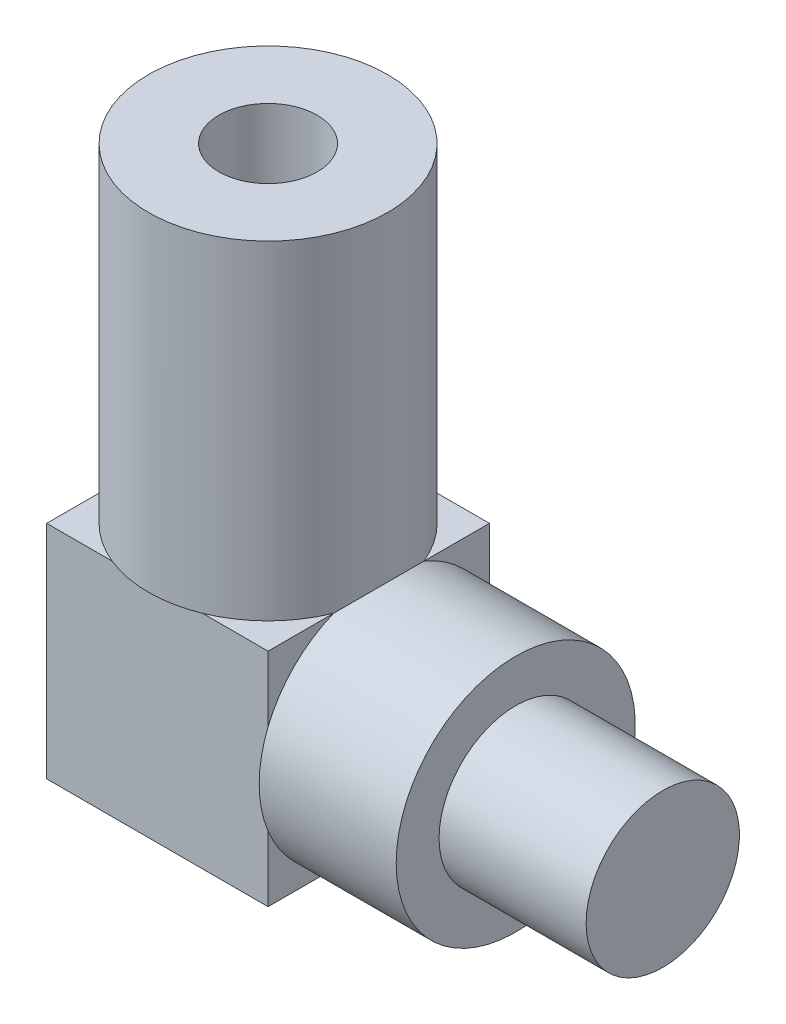
SolidWorks part; units mm, degrees
ref_plane "Front Plane" through (0, 0, 0) normal (0, 0, 1) x (1, 0, 0)
ref_plane "Top Plane" through (0, 0, 0) normal (0, 1, 0) x (1, 0, 0)
ref_plane "Right Plane" through (0, 0, 0) normal (1, 0, 0) x (0, 0, -1)
sketch "Block Sketch" plane through (0, 0, 0) normal (0, 0, 1) x (1, 0, 0)
  line L0 (-23.15, -7.15) -> (-8.85, -7.15)
  line L1 (-8.85, -7.15) -> (-8.85, 7.15)
  line L2 (-8.85, 7.15) -> (-23.15, 7.15)
  line L3 (-23.15, 7.15) -> (-23.15, -7.15)
extrude "Block" add sketch "Block Sketch" along normal mid plane 14.3
ref_axis "Engine Axis" through (11.1611, 0, 0) along (-1, 0, 0)
sketch "Neck and Stud Sketch" plane through (0, 0, 0) normal (0, 0, 1) x (1, 0, 0)
  line L0 (-1000, 0) -> (1000, 0) construction
  line L1 (9.5, 0) -> (9.5, 4.953)
  line L2 (9.5, 4.953) -> (0, 4.953)
  line L3 (0, 4.953) -> (0, 7.722)
  line L4 (0, 7.722) -> (-8.85, 7.722)
  line L5 (-8.85, 7.722) -> (-8.85, 0)
  line L6 (-8.85, 0) -> (9.5, 0)
revolve "Neck and Stud" add sketch "Neck and Stud Sketch" angle 360 about L0
sketch "Arm Sketch" plane through (0, 0, 0) normal (0, 0, 1) x (1, 0, 0)
  line L0 (-16, 0) -> (-16, 500) construction
  line L1 (-16, 7.15) -> (-8.278, 7.15)
  line L2 (-8.278, 7.15) -> (-8.278, 28.4)
  line L3 (-8.278, 28.4) -> (-16, 28.4)
  line L4 (-16, 28.4) -> (-16, 7.15)
revolve "Arm" add sketch "Arm Sketch" angle 360 about L0
sketch "Socket Sketch" plane through (0, 0, 0) normal (0, 0, 1) x (1, 0, 0)
  line L0 (-16, 0) -> (-16, 500) construction
  line L1 (-16, 13.2) -> (-12.825, 13.2)
  line L2 (-12.825, 13.2) -> (-12.825, 29.4)
  line L3 (-12.825, 29.4) -> (-16, 29.4)
  line L4 (-16, 29.4) -> (-16, 13.2)
revolve "Socket" cut sketch "Socket Sketch" angle 360 about L0
